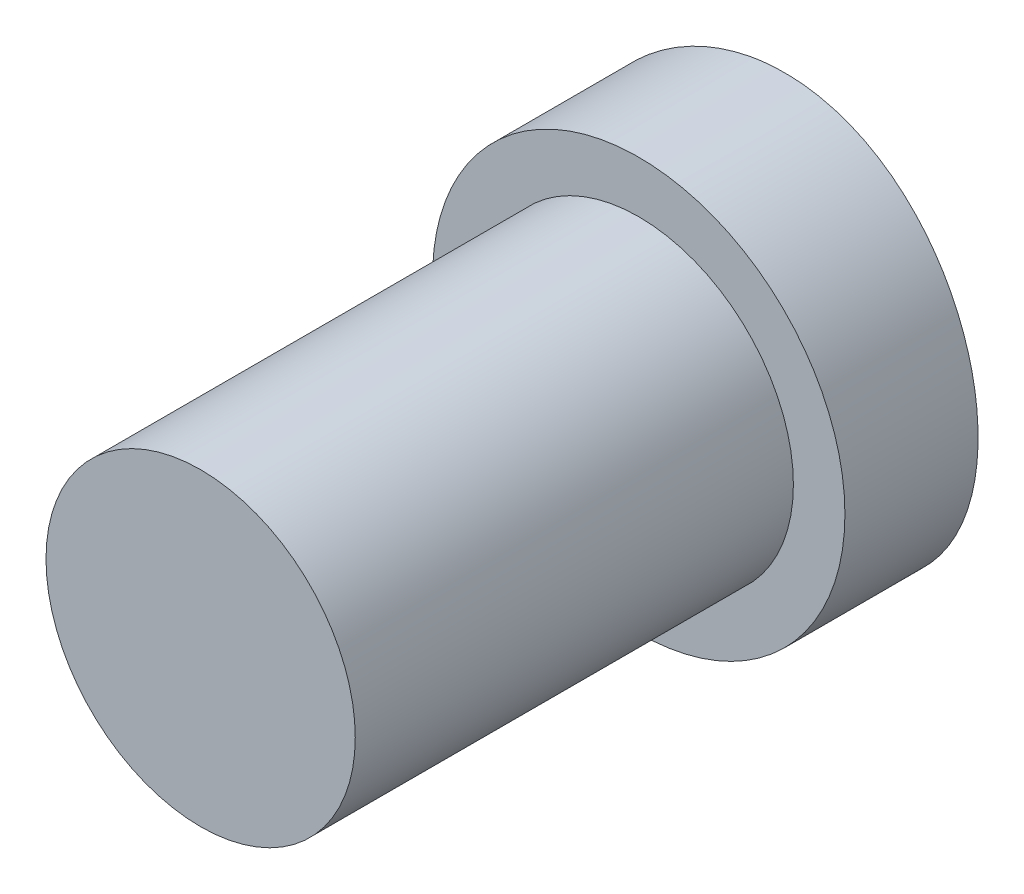
SolidWorks part; units mm, degrees
ref_plane "Front Plane" through (0, 0, 0) normal (0, 0, 1) x (1, 0, 0)
ref_plane "Top Plane" through (0, 0, 0) normal (0, 1, 0) x (1, 0, 0)
ref_plane "Right Plane" through (0, 0, 0) normal (1, 0, 0) x (0, 0, -1)
sketch "Sketch1" plane through (0, 0, 0) normal (0, 0, 1) x (1, 0, 0)
  circle A0 centre (0, 0) radius 4.5
  circle A1 centre (0, 0) radius 6
  dimension "D1" = 9
  dimension "D2" = 12
extrude "Boss-Extrude1" add sketch "Sketch1" along normal blind 17 contours A0 region at (0, 0, 0)
extrude "Boss-Extrude2" add sketch "Sketch1<4>" along normal blind 4.25
sketch "Sketch1<4>" plane through (0, 0, 0) normal (0, 0, 1) x (1, 0, 0) same geometry as "Sketch1"
sketch "Sketch2" plane through (0, 0, 0) normal (0, 1, 0) x (1, 0, 0)
  line L0 (0, 0) -> (0, 0.0029) construction
  line L2 (-6, -0.3745) -> (-6, 0)
  line L3 (-6, 0) -> (6, 0)
  line L4 (6, 0) -> (6, -0.3745)
  arc A0 (6, -0.3745) -> (-6, -0.3745) centre (0, -47.8755) ccw
  dimension "D1" = 0.3745
extrude "Cut-Extrude1" cut sketch "Sketch2" against normal mid plane 12 contours A0 L3 L2 | A0 L4 L3 | L3 L4 A0 L2 region at (4.5309, 0, 0.1127) region at (-4.5309, 0, 0.1127)
